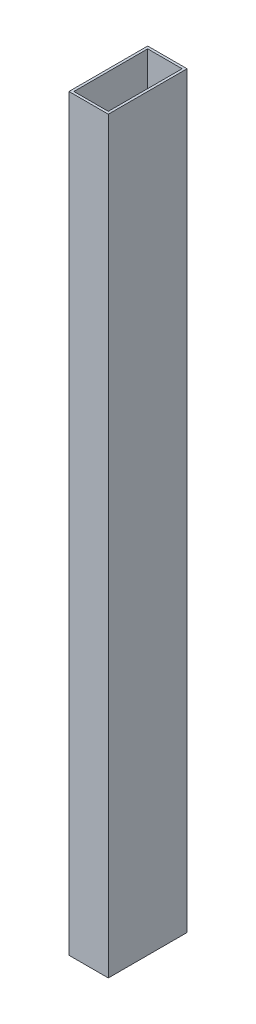
SolidWorks part; units mm, degrees
material "6061-T6 (SS)"
ref_plane "Front" through (0, 0, 0) normal (0, 0, 1) x (1, 0, 0)
ref_plane "Top" through (0, 0, 0) normal (0, 1, 0) x (1, 0, 0)
ref_plane "Right" through (0, 0, 0) normal (1, 0, 0) x (0, 0, -1)
sketch "Sketch1" plane through (0, 0, 0) normal (0, 1, 0) x (1, 0, 0)
  line L1 (12.7, 25.4) -> (-12.7, 25.4)
  line L2 (12.7, 25.4) -> (12.7, -25.4)
  line L3 (12.7, -25.4) -> (-12.7, -25.4)
  line L4 (-12.7, 25.4) -> (-12.7, -25.4)
  line L5 (12.7, 25.4) -> (-12.7, -25.4) construction
  line L6 (12.7, -25.4) -> (-12.7, 25.4) construction
  point P0 (0, 0)
  dimension "D1" = 25.4
  dimension "D2" = 50.8
extrude "Extrude-Thin1" add sketch "Sketch1" along normal up to surface (482.6 mm away) thin thin type one direction reverse wall 1.5875
